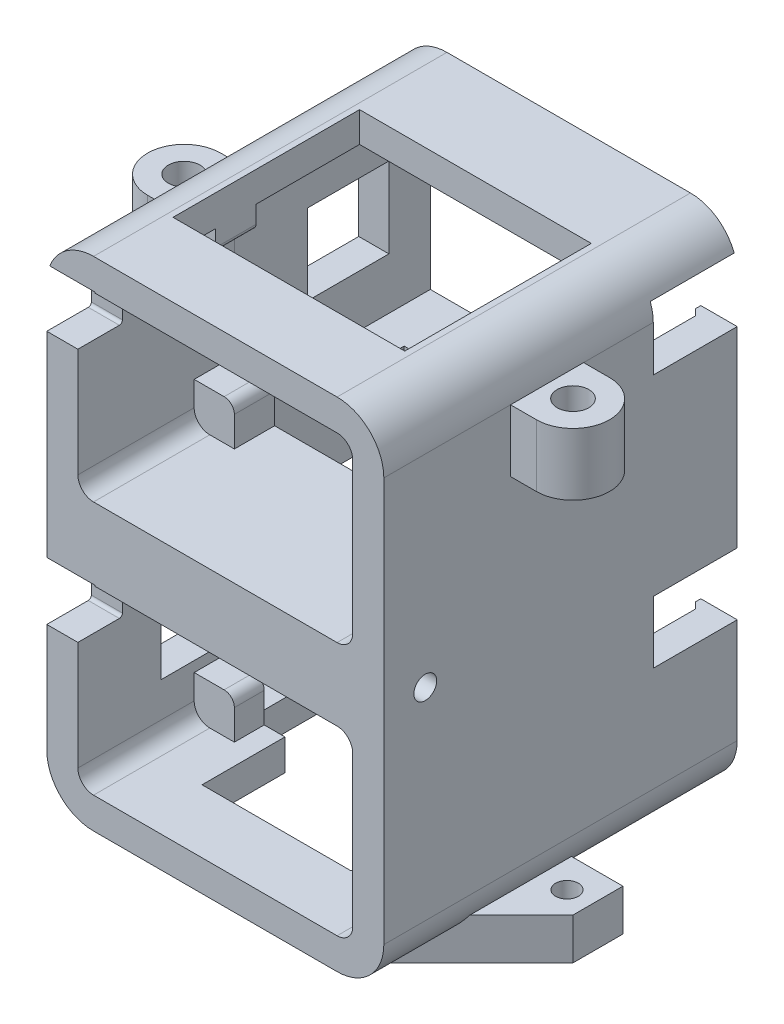
SolidWorks part; units mm, degrees
ref_plane "前视基准面" through (0, 0, 0) normal (0, 0, 1) x (1, 0, 0)
ref_plane "上视基准面" through (0, 0, 0) normal (0, 1, 0) x (1, 0, 0)
ref_plane "右视基准面" through (0, 0, 0) normal (1, 0, 0) x (0, 0, -1)
other "Configuration Table"
sketch "草图2" plane through (0, 0, 0) normal (0, 0, 1) x (1, 0, 0)
  line L20 (13.26, -7.25) -> (13.26, 7.25)
  line L21 (11.75, 8.76) -> (-16.76, 8.76)
  line L22 (-16.76, 8.76) -> (-16.76, 3.34)
  line L23 (-16.76, 3.34) -> (-13.26, 3.34)
  line L24 (-13.26, 3.34) -> (-13.26, -7.25)
  line L25 (-11.75, -8.76) -> (-3.99, -8.76)
  line L26 (-3.99, -8.76) -> (-3.99, -7.76)
  line L27 (-3.99, -7.76) -> (3.99, -7.76)
  line L28 (3.99, -7.76) -> (3.99, -8.76)
  line L29 (3.99, -8.76) -> (11.75, -8.76)
  line L40 (13.26, -7.25) -> (13.26, 7.25)
  line L41 (11.75, 8.76) -> (-16.76, 8.76)
  line L42 (-16.76, 8.76) -> (-16.76, 3.34)
  line L43 (-16.76, 3.34) -> (-13.26, 3.34)
  line L44 (-13.26, 3.34) -> (-13.26, -7.25)
  line L45 (-11.75, -8.76) -> (-3.99, -8.76)
  line L49 (3.99, -8.76) -> (11.75, -8.76)
  line L50 (-3.99, 15.74) -> (3.99, 15.74)
  line L51 (-3.99, -8.76) -> (3.99, -8.76)
  line L52 (-3.99, 12.74) -> (3.99, 12.74)
  line L53 (3.99, 12.74) -> (11.75, 12.74)
  line L54 (16.26, 17.25) -> (16.26, 31.75)
  line L55 (11.75, 36.26) -> (-19.76, 36.26)
  line L56 (-19.76, 36.26) -> (-19.76, 24.84)
  line L57 (-19.76, 24.84) -> (-16.26, 24.84)
  line L58 (-16.26, 24.84) -> (-16.26, 17.25)
  line L59 (-11.75, 12.74) -> (-3.99, 12.74)
  line L70 (13.26, 17.25) -> (13.26, 31.75)
  line L71 (11.75, 33.26) -> (-16.76, 33.26)
  line L72 (-16.76, 33.26) -> (-16.76, 27.84)
  line L73 (-16.76, 27.84) -> (-13.26, 27.84)
  line L74 (-13.26, 27.84) -> (-13.26, 17.25)
  line L75 (-11.75, 15.74) -> (-3.99, 15.74)
  line L76 (-3.99, 15.74) -> (-3.99, 16.74)
  line L77 (-3.99, 16.74) -> (3.99, 16.74)
  line L78 (3.99, 16.74) -> (3.99, 15.74)
  line L79 (3.99, 15.74) -> (11.75, 15.74)
  line L80 (13.26, 17.25) -> (13.26, 31.75)
  line L81 (11.75, 33.26) -> (-16.76, 33.26)
  line L82 (-16.76, 33.26) -> (-16.76, 27.84)
  line L83 (-16.76, 27.84) -> (-13.26, 27.84)
  line L84 (-13.26, 27.84) -> (-13.26, 17.25)
  line L85 (-11.75, 15.74) -> (-3.99, 15.74)
  line L89 (3.99, 15.74) -> (11.75, 15.74)
  line L90 (16.26, -7.25) -> (16.26, 7.25)
  line L91 (11.75, 11.76) -> (-19.76, 11.76)
  line L92 (-19.76, 11.76) -> (-19.76, 0.34)
  line L93 (-19.76, 0.34) -> (-16.26, 0.34)
  line L94 (-16.26, 0.34) -> (-16.26, -7.25)
  line L95 (-11.75, -11.76) -> (-3.99, -11.76)
  line L96 (-3.99, -11.76) -> (3.99, -11.76)
  line L97 (3.99, -11.76) -> (11.75, -11.76)
  line L98 (-16.26, 0.34) -> (-16.26, 3.34)
  line L99 (-16.26, 17.25) -> (-16.26, 11.76)
  line L100 (16.26, 17.25) -> (16.26, 7.25)
  line L101 (-16.76, 33.26) -> (-19.76, 33.26)
  line L102 (-16.76, 27.84) -> (-19.76, 27.84)
  line L103 (-16.76, 8.76) -> (-19.76, 8.76)
  line L104 (-16.26, 24.84) -> (-16.26, 27.84)
  line L105 (-16.26, 36.26) -> (-16.26, 33.26)
  line L106 (-16.26, 11.76) -> (-16.26, 8.76)
  line L107 (-16.26, 33.26) -> (-16.26, 27.84)
  line L108 (-16.26, 8.76) -> (-16.26, 3.34)
  line L109 (-13.26, 27.84) -> (-13.26, 33.26)
  line L110 (-13.26, 3.34) -> (-13.26, 8.76)
  arc A1 (-11.75, 11.76) -> (-16.26, 7.25) centre (-11.75, 7.25) ccw
  arc A2 (-11.75, 8.76) -> (-13.26, 7.25) centre (-11.75, 7.25) ccw
  arc A3 (-11.75, 8.76) -> (-13.26, 7.25) centre (-11.75, 7.25) ccw
  arc A6 (13.26, 7.25) -> (11.75, 8.76) centre (11.75, 7.25) ccw
  arc A7 (-13.26, -7.25) -> (-11.75, -8.76) centre (-11.75, -7.25) ccw
  arc A8 (11.75, -8.76) -> (13.26, -7.25) centre (11.75, -7.25) ccw
  arc A12 (13.26, 7.25) -> (11.75, 8.76) centre (11.75, 7.25) ccw
  arc A13 (-13.26, -7.25) -> (-11.75, -8.76) centre (-11.75, -7.25) ccw
  arc A14 (11.75, -8.76) -> (13.26, -7.25) centre (11.75, -7.25) ccw
  arc A15 (11.75, 12.74) -> (16.26, 17.25) centre (11.75, 17.25) ccw
  arc A16 (16.26, 31.75) -> (11.75, 36.26) centre (11.75, 31.75) ccw
  arc A17 (-16.26, 17.25) -> (-11.75, 12.74) centre (-11.75, 17.25) ccw
  arc A21 (13.26, 31.75) -> (11.75, 33.26) centre (11.75, 31.75) ccw
  arc A22 (-13.26, 17.25) -> (-11.75, 15.74) centre (-11.75, 17.25) ccw
  arc A23 (11.75, 15.74) -> (13.26, 17.25) centre (11.75, 17.25) ccw
  arc A24 (13.26, 31.75) -> (11.75, 33.26) centre (11.75, 31.75) ccw
  arc A25 (-13.26, 17.25) -> (-11.75, 15.74) centre (-11.75, 17.25) ccw
  arc A26 (11.75, 15.74) -> (13.26, 17.25) centre (11.75, 17.25) ccw
  arc A27 (16.26, 7.25) -> (11.75, 11.76) centre (11.75, 7.25) ccw
  arc A28 (-16.26, -7.25) -> (-11.75, -11.76) centre (-11.75, -7.25) ccw
  arc A29 (11.75, -11.76) -> (16.26, -7.25) centre (11.75, -7.25) ccw
  arc A31 (-11.75, 36.26) -> (-16.26, 31.75) centre (-11.75, 31.75) ccw
  arc A32 (-11.75, 33.26) -> (-13.26, 31.75) centre (-11.75, 31.75) ccw
  arc A33 (-11.75, 33.26) -> (-13.26, 31.75) centre (-11.75, 31.75) ccw
  dimension "D3" = 3
  dimension "D4" = 3
  dimension "D5" = 0.01
  dimension "D6" = 3
  dimension "D7" = 0.01
  dimension "D8" = 3
extrude "凸台-拉伸2" add sketch "草图2" against normal up to surface (11.22 mm away)
sketch "草图3" plane through (0, 0, -11.22) normal (0, 0, -1) x (-1, 0, 0)
  line L0 (11.75, -8.76) -> (-11.75, -8.76) construction
  line L2 (-11.75, 8.76) -> (11.75, 8.76) construction
  line L3 (11.75, -8.76) -> (-11.75, -8.76)
  line L4 (16.26, -7.25) -> (16.26, 31.75)
  line L5 (11.75, 36.26) -> (-11.75, 36.26)
  line L6 (-16.26, 31.75) -> (-16.26, -7.25)
  line L7 (-11.75, -11.76) -> (11.75, -11.76)
  line L12 (16.26, -7.25) -> (16.26, 31.75)
  line L13 (11.75, 36.26) -> (-11.75, 36.26)
  line L14 (-16.26, 31.75) -> (-16.26, -7.25)
  line L16 (-11.75, -11.76) -> (11.75, -11.76)
  line L20 (-13.26, -7.25) -> (-13.26, 7.25)
  line L21 (-11.75, 33.26) -> (11.75, 33.26) construction
  line L22 (-13.26, 17.25) -> (-13.26, 31.75) construction
  line L23 (-9.38, -8.74) -> (-9.38, -5.87)
  line L24 (-10.37, -4.88) -> (-13.24, -4.88)
  line L25 (-13.24, -4.88) -> (-13.24, -7.25)
  line L26 (-11.75, -8.74) -> (-9.38, -8.74)
  line L27 (-9.38, -8.74) -> (-9.38, -5.87)
  line L28 (-10.37, -4.88) -> (-13.24, -4.88)
  line L32 (11.75, 15.74) -> (-11.75, 15.74) construction
  line L33 (-11.75, 33.26) -> (11.75, 33.26)
  line L34 (-13.26, 17.25) -> (-13.26, 31.75)
  line L36 (11.75, 15.74) -> (-11.75, 15.74)
  line L38 (13.26, 7.25) -> (13.26, -7.25) construction
  line L39 (13.24, -4.88) -> (10.37, -4.88)
  line L40 (9.38, -5.87) -> (9.38, -8.74)
  line L41 (9.38, -8.74) -> (11.75, -8.74)
  line L42 (13.24, -7.25) -> (13.24, -4.88)
  line L43 (13.24, -4.88) -> (10.37, -4.88)
  line L44 (9.38, -5.87) -> (9.38, -8.74)
  line L47 (13.26, 7.25) -> (13.26, -7.25)
  line L48 (-11.75, 8.76) -> (11.75, 8.76) construction
  line L49 (-9.38, 15.75) -> (-9.38, 18.63)
  line L50 (-10.37, 19.62) -> (-13.25, 19.62)
  line L51 (-13.24, 6.68) -> (-11.67, 6.68)
  line L52 (-11.18, 7.17) -> (-11.18, 8.74)
  line L53 (-11.18, 8.74) -> (-11.75, 8.74)
  line L54 (-13.24, 7.25) -> (-13.24, 6.68)
  line L55 (-13.24, 6.68) -> (-11.67, 6.68)
  line L56 (-11.18, 7.17) -> (-11.18, 8.74)
  line L59 (-13.24, 6.68) -> (-13.26, 6.68)
  line L60 (-13.26, -7.25) -> (-13.26, 7.25) construction
  line L61 (-9.38, 15.74) -> (-9.38, 18.63)
  line L62 (-10.37, 19.62) -> (-13.26, 19.62)
  line L63 (11.18, 8.74) -> (11.18, 7.17)
  line L64 (11.67, 6.68) -> (13.24, 6.68)
  line L65 (13.24, 6.68) -> (13.24, 7.25)
  line L66 (11.75, 8.74) -> (11.18, 8.74)
  line L67 (11.18, 8.76) -> (11.18, 7.17)
  line L68 (11.67, 6.68) -> (13.26, 6.68)
  line L71 (-11.75, 8.76) -> (11.75, 8.76)
  line L73 (-13.25, 31.18) -> (-11.67, 31.18)
  line L74 (-11.18, 31.67) -> (-11.18, 33.25)
  line L75 (-13.25, 31.18) -> (-11.67, 31.18)
  line L76 (-11.18, 31.67) -> (-11.18, 33.25)
  line L79 (11.67, 31.18) -> (13.25, 31.18)
  line L80 (11.18, 33.25) -> (11.18, 31.67)
  line L81 (11.67, 31.18) -> (13.26, 31.18)
  line L82 (11.18, 33.25) -> (11.18, 31.67)
  line L83 (-13.25, 31.18) -> (-13.26, 31.18)
  line L84 (-11.18, 33.25) -> (-11.18, 33.26)
  line L85 (9.38, 18.63) -> (9.38, 15.75)
  line L86 (13.25, 19.62) -> (10.37, 19.62)
  line L87 (9.38, 18.63) -> (9.38, 15.74)
  line L88 (13.26, 19.62) -> (10.37, 19.62)
  line L89 (11.18, 33.25) -> (11.18, 33.26)
  line L90 (-11.18, 8.74) -> (-11.18, 8.76)
  line L91 (13.26, 31.75) -> (13.26, 17.25) construction
  line L92 (13.26, 31.75) -> (13.26, 17.25)
  line L93 (-13.24, -4.88) -> (-13.26, -4.88)
  line L94 (-9.38, -8.74) -> (-9.38, -8.76)
  line L95 (9.38, -8.74) -> (9.38, -8.76)
  line L96 (13.24, -4.88) -> (13.26, -4.88)
  arc A0 (-13.26, -7.25) -> (-11.75, -8.76) centre (-11.75, -7.25) ccw construction
  arc A1 (11.75, -8.76) -> (13.26, -7.25) centre (11.75, -7.25) ccw construction
  arc A2 (-11.75, 8.76) -> (-13.26, 7.25) centre (-11.75, 7.25) ccw construction
  arc A3 (11.75, -11.76) -> (16.26, -7.25) centre (11.75, -7.25) ccw
  arc A4 (-11.75, 36.26) -> (-16.26, 31.75) centre (-11.75, 31.75) ccw
  arc A5 (-16.26, -7.25) -> (-11.75, -11.76) centre (-11.75, -7.25) ccw
  arc A6 (11.75, -11.76) -> (16.26, -7.25) centre (11.75, -7.25) ccw
  arc A9 (-11.75, 36.26) -> (-16.26, 31.75) centre (-11.75, 31.75) ccw
  arc A10 (-9.38, -5.87) -> (-10.37, -4.88) centre (-10.37, -5.87) ccw
  arc A11 (-13.24, -7.25) -> (-11.75, -8.74) centre (-11.75, -7.25) ccw
  arc A12 (-9.38, -5.87) -> (-10.37, -4.88) centre (-10.37, -5.87) ccw
  arc A14 (-16.26, -7.25) -> (-11.75, -11.76) centre (-11.75, -7.25) ccw
  arc A15 (-13.26, -7.25) -> (-11.75, -8.76) centre (-11.75, -7.25) ccw
  arc A16 (11.75, -8.76) -> (13.26, -7.25) centre (11.75, -7.25) ccw
  arc A17 (-11.75, 8.76) -> (-13.26, 7.25) centre (-11.75, 7.25) ccw
  arc A18 (10.37, -4.88) -> (9.38, -5.87) centre (10.37, -5.87) ccw
  arc A19 (11.75, -8.74) -> (13.24, -7.25) centre (11.75, -7.25) ccw
  arc A20 (10.37, -4.88) -> (9.38, -5.87) centre (10.37, -5.87) ccw
  arc A22 (-11.75, 33.26) -> (-13.26, 31.75) centre (-11.75, 31.75) ccw construction
  arc A23 (11.75, 15.74) -> (13.26, 17.25) centre (11.75, 17.25) ccw construction
  arc A24 (-11.67, 6.68) -> (-11.18, 7.17) centre (-11.67, 7.17) ccw
  arc A25 (-11.75, 8.74) -> (-13.24, 7.25) centre (-11.75, 7.25) ccw
  arc A26 (-11.67, 6.68) -> (-11.18, 7.17) centre (-11.67, 7.17) ccw
  arc A28 (-13.26, 17.25) -> (-11.75, 15.74) centre (-11.75, 17.25) ccw construction
  arc A29 (-11.75, 33.26) -> (-13.26, 31.75) centre (-11.75, 31.75) ccw
  arc A30 (11.18, 7.17) -> (11.67, 6.68) centre (11.67, 7.17) ccw
  arc A31 (13.24, 7.25) -> (11.75, 8.74) centre (11.75, 7.25) ccw
  arc A32 (11.18, 7.17) -> (11.67, 6.68) centre (11.67, 7.17) ccw
  arc A34 (11.75, 15.74) -> (13.26, 17.25) centre (11.75, 17.25) ccw
  arc A35 (-13.26, 17.25) -> (-11.75, 15.74) centre (-11.75, 17.25) ccw
  arc A36 (13.26, 7.25) -> (11.75, 8.76) centre (11.75, 7.25) ccw construction
  arc A37 (13.26, 7.25) -> (11.75, 8.76) centre (11.75, 7.25) ccw
  arc A38 (-9.38, 18.63) -> (-10.37, 19.62) centre (-10.37, 18.63) ccw
  arc A39 (-9.38, 18.63) -> (-10.37, 19.62) centre (-10.37, 18.63) ccw
  arc A41 (-11.67, 31.18) -> (-11.18, 31.67) centre (-11.67, 31.67) ccw
  arc A42 (-11.67, 31.18) -> (-11.18, 31.67) centre (-11.67, 31.67) ccw
  arc A44 (11.18, 31.67) -> (11.67, 31.18) centre (11.67, 31.67) ccw
  arc A45 (11.18, 31.67) -> (11.67, 31.18) centre (11.67, 31.67) ccw
  arc A46 (13.26, 31.75) -> (11.75, 33.26) centre (11.75, 31.75) ccw construction
  arc A47 (10.37, 19.62) -> (9.38, 18.63) centre (10.37, 18.63) ccw
  arc A48 (10.37, 19.62) -> (9.38, 18.63) centre (10.37, 18.63) ccw
  arc A49 (13.26, 31.75) -> (11.75, 33.26) centre (11.75, 31.75) ccw
  arc A52 (16.26, 31.75) -> (11.75, 36.26) centre (11.75, 31.75) ccw
  arc A53 (16.26, 31.75) -> (11.75, 36.26) centre (11.75, 31.75) ccw
  dimension "D7" = 0.01
  dimension "D9" = 0.01
extrude "凸台-拉伸3" add sketch "草图3" along normal up to surface (3.88 mm away)
sketch "草图4" plane through (-16.26, 0, 0) normal (-1, 0, 0) x (0, 0, 1)
  line L8 (0.1, 8.85) -> (-4, 8.85)
  line L9 (-4.3, 8.55) -> (-4.3, 3.55)
  line L10 (-4, 3.25) -> (0.1, 3.25)
  line L11 (0.1, 3.25) -> (0.1, 8.85)
  line L12 (0.1, 8.85) -> (-4, 8.85)
  line L13 (-4.3, 8.55) -> (-4.3, 3.55)
  line L14 (-4, 3.25) -> (0.1, 3.25)
  line L15 (0.1, 3.25) -> (0.1, 8.85)
  line L20 (0.1, 33.35) -> (-4, 33.35)
  line L21 (-4.3, 33.05) -> (-4.3, 28.05)
  line L22 (-4, 27.75) -> (0.1, 27.75)
  line L23 (0.1, 27.75) -> (0.1, 33.35)
  line L24 (0.1, 33.35) -> (-4, 33.35)
  line L25 (-4.3, 33.05) -> (-4.3, 28.05)
  line L26 (-4, 27.75) -> (0.1, 27.75)
  line L27 (0.1, 27.75) -> (0.1, 33.35)
  arc A4 (-4, 8.85) -> (-4.3, 8.55) centre (-4, 8.55) ccw
  arc A5 (-4.3, 3.55) -> (-4, 3.25) centre (-4, 3.55) ccw
  arc A6 (-4, 8.85) -> (-4.3, 8.55) centre (-4, 8.55) ccw
  arc A7 (-4.3, 3.55) -> (-4, 3.25) centre (-4, 3.55) ccw
  arc A10 (-4, 33.35) -> (-4.3, 33.05) centre (-4, 33.05) ccw
  arc A11 (-4.3, 28.05) -> (-4, 27.75) centre (-4, 28.05) ccw
  arc A12 (-4, 33.35) -> (-4.3, 33.05) centre (-4, 33.05) ccw
  arc A13 (-4.3, 28.05) -> (-4, 27.75) centre (-4, 28.05) ccw
  dimension "D1" = 0.1
extrude "切除-拉伸1" cut sketch "草图4" against normal blind 4.65
ref_plane "基准面1" through (0, 31.75, 0) normal (0, 1, 0) x (1, 0, 0)
sketch "草图8" plane through (0, 31.75, 0) normal (0, 1, 0) x (1, 0, 0)
  line L0 (18.76, 12.23) -> (15.235, 12.23)
  line L1 (15.235, 12.23) -> (15.235, 15.755)
  line L2 (16.26, 15.1) -> (16.26, 0) construction
  line L3 (-12.113, 15.755) -> (15.235, 15.755) construction
  line L4 (9.73, 15.91) -> (-9.73, 15.91) construction
  line L5 (-9.73, 15.6) -> (9.73, 15.6) construction
  line L9 (18.76, 19.28) -> (15.235, 19.28)
  line L10 (15.235, 15.755) -> (15.235, 19.28)
  circle A2 centre (18.76, 15.755) radius 1.525
  circle A3 centre (18.76, 15.755) radius 3.525
  dimension "D1" = 3.05
  dimension "D3" = 2.5
  dimension "D2" = 2
extrude "凸台-拉伸5" add sketch "草图8" against normal blind 6 contours A3 A2 | A3 L9 L10 | A3 L1 L0
mirror "镜向1" about plane through (0, 0, 0) normal (1, 0, 0) of "凸台-拉伸5"
sketch "草图9" plane through (0, 0, -15.1) normal (0, 0, -1) x (-1, 0, 0)
  line L0 (-11.18, 33.26) -> (11.18, 33.26) construction
  line L1 (-11.18, 33.26) -> (11.18, 33.26)
  line L2 (-11.18, 33.26) -> (-11.18, 36.26)
  line L3 (-11.18, 36.26) -> (11.18, 36.26)
  line L4 (11.18, 33.26) -> (11.18, 36.26)
  line L5 (11.75, 36.26) -> (-11.75, 36.26) construction
  line L6 (-11.18, 31.67) -> (-11.18, 33.26) construction
  line L7 (11.18, 33.26) -> (11.18, 31.67) construction
extrude "切除-拉伸3" cut sketch "草图9" against normal blind 8
sketch "草图10" plane through (0, 0, -15.1) normal (0, 0, -1) x (-1, 0, 0)
  line L0 (-11.75, -11.76) -> (11.75, -11.76) construction
  line L1 (-10.73, -11.76) -> (10.73, -11.76)
  line L2 (-10.73, -11.76) -> (-10.73, -4.88)
  line L3 (-10.73, -4.88) -> (10.73, -4.88)
  line L4 (10.73, -11.76) -> (10.73, -4.88)
  line L5 (13.26, -4.88) -> (10.37, -4.88) construction
  line L6 (-9.73, 21.7989) -> (-9.73, 20.8989) construction
  line L7 (9.73, 69.5489) -> (9.73, -48.1511) construction
  dimension "D1" = 1
  dimension "D2" = 1
extrude "切除-拉伸4" cut sketch "草图10" against normal blind 1
sketch "草图12" plane through (-16.26, 0, 0) normal (-1, 0, 0) x (0, 0, 1)
  line L0 (0, 8.85) -> (0, 27.75) construction
  line L1 (-11.22, 8.76) -> (-4.2142, 8.76) construction
  line L2 (-11.22, 15.74) -> (0, 15.74) construction
  line L3 (-11.22, 8.76) -> (-4.2142, 8.76)
  line L4 (-11.22, 15.74) -> (0, 15.74)
  line L5 (-8.8508, 12.25) -> (0.722, 12.25) construction
  circle A0 centre (-4, 12.25) radius 1.1
  dimension "D1" = 2.2
  dimension "D2" = 4
extrude "切除-拉伸5" cut sketch "草图12" against normal blind 8 contours A0 L5 | L5 A0
mirror "镜向2" about plane through (0, 0, 0) normal (1, 0, 0) of "切除-拉伸5"
sketch "草图14" plane through (0, 0, -15.1) normal (0, 0, -1) x (-1, 0, 0)
  line L0 (-16.26, 19.53) -> (16.26, 19.53)
  line L2 (-16.26, 8.85) -> (16.26, 8.85)
  line L3 (-10.37, 19.63) -> (-13.25, 19.63) construction
  line L6 (9.88, -48.3011) -> (9.88, 69.6193)
  line L7 (-9.88, -48.3011) -> (9.88, -48.3011)
  line L8 (-9.88, 69.6193) -> (-9.88, -48.3011)
  line L9 (9.88, -48.3011) -> (9.88, 69.6193)
  line L10 (-9.88, -48.3011) -> (9.88, -48.3011)
  line L11 (-9.88, 69.6193) -> (-9.88, -48.3011)
  line L13 (-11.17, 8.75) -> (11.17, 8.75) construction
  line L19 (16.26, 3.25) -> (13.26, 3.25)
  line L20 (16.26, -7.25) -> (16.26, 3.25)
  line L21 (-11.75, -11.76) -> (11.75, -11.76)
  line L22 (-16.26, 31.75) -> (-16.26, -7.25)
  line L23 (11.75, 36.26) -> (-11.75, 36.26)
  line L24 (11.61, 33.35) -> (15.9666, 33.35)
  line L26 (-11.75, 33.26) -> (11.61, 33.26)
  line L27 (-13.26, 17.25) -> (-13.26, 31.75)
  line L28 (11.75, 15.74) -> (-11.75, 15.74)
  line L29 (13.26, 27.75) -> (13.26, 17.25)
  line L30 (16.26, 27.75) -> (13.26, 27.75)
  line L31 (16.26, 8.85) -> (16.26, 27.75)
  line L32 (11.61, 8.85) -> (16.26, 8.85)
  line L34 (-11.75, 8.76) -> (11.61, 8.76)
  line L35 (-13.26, -7.25) -> (-13.26, 7.25)
  line L36 (11.75, -8.76) -> (-11.75, -8.76)
  line L37 (13.26, 3.25) -> (13.26, -7.25)
  line L39 (16.26, -7.25) -> (16.26, 8.85)
  line L40 (-11.75, -11.76) -> (11.75, -11.76)
  line L41 (-16.26, 31.75) -> (-16.26, -7.25)
  line L42 (11.75, 36.26) -> (-11.75, 36.26)
  line L50 (16.26, 8.85) -> (16.26, 31.75)
  line L66 (11.61, 33.26) -> (11.61, 33.35)
  line L67 (11.61, 8.76) -> (11.61, 8.85)
  arc A2 (9.88, 69.6193) -> (-9.88, 69.6193) centre (0, 57.7742) ccw
  arc A3 (9.88, 69.6193) -> (-9.88, 69.6193) centre (0, 57.7742) ccw
  arc A10 (11.75, -11.76) -> (16.26, -7.25) centre (11.75, -7.25) ccw
  arc A11 (-16.26, -7.25) -> (-11.75, -11.76) centre (-11.75, -7.25) ccw
  arc A12 (-11.75, 36.26) -> (-16.26, 31.75) centre (-11.75, 31.75) ccw
  arc A13 (15.9666, 33.35) -> (11.75, 36.26) centre (11.75, 31.75) ccw
  arc A14 (-11.75, 33.26) -> (-13.26, 31.75) centre (-11.75, 31.75) ccw
  arc A15 (-13.26, 17.25) -> (-11.75, 15.74) centre (-11.75, 17.25) ccw
  arc A16 (11.75, 15.74) -> (13.26, 17.25) centre (11.75, 17.25) ccw
  arc A17 (-11.75, 8.76) -> (-13.26, 7.25) centre (-11.75, 7.25) ccw
  arc A18 (-13.26, -7.25) -> (-11.75, -8.76) centre (-11.75, -7.25) ccw
  arc A19 (11.75, -8.76) -> (13.26, -7.25) centre (11.75, -7.25) ccw
  arc A20 (11.75, -11.76) -> (16.26, -7.25) centre (11.75, -7.25) ccw
  arc A21 (-16.26, -7.25) -> (-11.75, -11.76) centre (-11.75, -7.25) ccw
  arc A22 (-11.75, 36.26) -> (-16.26, 31.75) centre (-11.75, 31.75) ccw
  arc A23 (16.26, 31.75) -> (11.75, 36.26) centre (11.75, 31.75) ccw
  dimension "D3" = 0.1
  dimension "D4" = 0.1
  dimension "D2" = 0.15
extrude "凸台-拉伸7" add sketch "草图14" along normal blind 3
sketch "草图15" plane through (0, 0, -15.1) normal (0, 0, -1) x (-1, 0, 0)
  line L0 (-16.26, 25.75) -> (-16.26, 19.53) construction
  line L7 (-16.26, 19.53) -> (-16.26, 8.85) construction
  line L8 (-16.26, 8.85) -> (-16.26, -7.25) construction
  line L10 (-10.73, -11.76) -> (10.73, -11.76) construction
  line L22 (16.26, -7.25) -> (16.26, 8.85) construction
  line L23 (16.26, 8.85) -> (16.26, 19.53) construction
  line L32 (16.26, 19.53) -> (16.26, 25.75) construction
  line L37 (11.18, 36.26) -> (-11.18, 36.26) construction
  line L38 (-16.26, 31.75) -> (-16.26, 19.53)
  line L39 (-16.26, 19.53) -> (-16.26, 8.85)
  line L42 (-16.26, 8.85) -> (-16.26, -7.25)
  line L43 (-11.75, -11.76) -> (11.75, -11.76)
  line L44 (16.26, -7.25) -> (16.26, 8.85)
  line L45 (16.26, 8.85) -> (16.26, 19.53)
  line L46 (16.26, 19.53) -> (16.26, 31.75)
  line L47 (11.75, 36.26) -> (-11.75, 36.26)
  line L48 (-11.17, 33.25) -> (11.17, 33.25) construction
  line L49 (-13.35, 33.35) -> (13.35, 33.35)
  line L54 (-13.35, 33.35) -> (-13.35, -8.85)
  line L55 (-13.35, -8.85) -> (13.35, -8.85)
  line L56 (13.35, 33.35) -> (13.35, -8.85)
  line L58 (13.25, 6.67) -> (13.25, -4.87) construction
  line L59 (9.37, -8.75) -> (-9.37, -8.75) construction
  line L60 (-13.25, -4.87) -> (-13.25, 6.67) construction
  arc A8 (-16.26, -7.25) -> (-11.75, -11.76) centre (-11.75, -7.25) ccw construction
  arc A9 (11.75, -11.76) -> (16.26, -7.25) centre (11.75, -7.25) ccw construction
  arc A10 (16.26, 31.75) -> (11.75, 36.26) centre (11.75, 31.75) ccw construction
  arc A11 (-11.75, 36.26) -> (-16.26, 31.75) centre (-11.75, 31.75) ccw construction
  arc A12 (-16.26, -7.25) -> (-11.75, -11.76) centre (-11.75, -7.25) ccw
  arc A13 (11.75, -11.76) -> (16.26, -7.25) centre (11.75, -7.25) ccw
  arc A14 (16.26, 31.75) -> (11.75, 36.26) centre (11.75, 31.75) ccw
  arc A15 (-11.75, 36.26) -> (-16.26, 31.75) centre (-11.75, 31.75) ccw
  point P2 (13.45, 33.102)
  point P29 (-13.45, 33.1809)
  point P38 (-13.45, 15.55)
  dimension "D2" = 0.1
  dimension "D1" = 0.1
  dimension "D3" = 0.1
  dimension "D4" = 0.1
extrude "凸台-上半部分" add sketch "草图15" along normal blind 19
sketch "草图16" plane through (0, 0, -18.1) normal (0, 0, -1) x (-1, 0, 0)
  line L1 (-13.35, 8.85) -> (13.35, 8.85)
  line L2 (-13.35, 8.85) -> (-13.35, 15.65)
  line L3 (-13.35, 15.65) -> (13.35, 15.65)
  line L4 (13.35, 8.85) -> (13.35, 15.65)
  line L12 (-13.35, 33.35) -> (-13.35, -8.85) construction
  line L13 (13.35, 33.35) -> (13.35, -8.85) construction
  line L15 (-4, 15.75) -> (-11.75, 15.75) construction
  line L16 (-11.17, 8.75) -> (11.17, 8.75) construction
  point P4 (0, 0)
  point P5 (-13.45, 15.74)
  point P7 (13.45, 8.76)
  point P12 (0, 0)
  dimension "D2" = 0.1
  dimension "D1" = 0.1
extrude "凸台-拉伸9" add sketch "草图16" along normal up to surface (16 mm away) up to face at (0, 12.25, -34.1)
sketch "草图11" plane through (0, -13.58, 0) normal (0, 1, 0) x (1, 0, 0)
  line L2 (11.75, 34.1) -> (11.75, 0)
  line L3 (11.75, 34.1) -> (11.75, 0) construction
  line L7 (15.88, 21.655) -> (15.88, 16.405)
  line L8 (15.88, 16.405) -> (17.4201, 16.405)
  line L9 (17.4201, 15.105) -> (15.88, 15.105)
  line L10 (15.88, 15.105) -> (15.88, 9.855)
  line L11 (15.88, 9.855) -> (20.58, 9.855)
  line L12 (20.58, 9.855) -> (20.58, 21.655)
  line L13 (20.58, 21.655) -> (15.88, 21.655)
  line L19 (20.58, 13.9124) -> (20.58, 18.755)
  line L21 (11.75, 18.755) -> (20.58, 18.755)
  line L22 (20.58, 13.9124) -> (11.75, 5.0824)
  circle A0 centre (18.18, 15.755) radius 1.1
  arc A1 (17.4201, 15.105) -> (17.4201, 16.405) centre (18.18, 15.755) ccw
  line M15 (15.88, 21.655) -> (15.88, 16.405)
  line M16 (15.88, 16.405) -> (17.4201, 16.405)
  line M18 (17.4201, 15.105) -> (15.88, 15.105)
  line M19 (15.88, 15.105) -> (15.88, 9.855)
  line M20 (15.88, 9.855) -> (20.58, 9.855)
  line M21 (20.58, 9.855) -> (20.58, 21.655)
  dimension "D6" = 2.2
  dimension "D2" = 3
  dimension "D5" = 45
  dimension "D7" = 3
  dimension "D1" = 0
extrude "凸台-舵机固定孔位" add sketch "草图11" along normal blind 4 contours A0 L21 L2 L22 M16 M15 M20 M19 M18 | A0 L22 L21 M18 M19 M20 M21 M15 M16
sketch "草图17" plane through (0, 8.85, 0) normal (0, -1, 0) x (1, 0, 0)
  line L2 (11.75, -34.1) -> (-11.75, -34.1) construction
  line L3 (-9.88, -18.1) -> (9.88, -18.1)
  line L5 (-9.88, -18.1) -> (9.88, -18.1)
  line L6 (-9.88, -18.1) -> (-9.88, -28.1)
  line L7 (-9.88, -28.1) -> (9.88, -28.1)
  line L8 (9.88, -18.1) -> (9.88, -28.1)
  line L9 (9.88, -18.1) -> (9.88, -15.1) construction
  line L10 (9.88, -18.1) -> (-9.88, -18.1) construction
  line L12 (-9.88, -18.1) -> (-9.88, -15.1) construction
  point P1 (9.88, -18.1)
  point P2 (9.88, -18.1)
  point P4 (0, 0)
  point P12 (-10.2095, -18.1)
  point P13 (-9.88, -18.1)
  point P15 (0, 0)
  point P16 (0, 0)
  point P17 (9.88, -17.8358)
  point P20 (9.88, -18.1489)
  point P21 (9.88, -18.1)
  point P26 (-9.88, -18.1)
  dimension "D1" = 6
extrude "切除-拉伸8" cut sketch "草图17" against normal up to next contours L8 L3 L6 L7
sketch "草图18" plane through (13.35, 0, 0) normal (-1, 0, 0) x (0, 0, 1)
  line L0 (0, -7.25) -> (0, 31.75) construction
  line L1 (-34.1, 2.85) -> (-26, 2.85)
  line L2 (-34.1, 2.85) -> (-34.1, 8.85)
  line L3 (-34.1, 8.85) -> (-26, 8.85)
  line L4 (-26, 2.85) -> (-26, 8.85)
  line L5 (-34.1, 27.35) -> (-26, 27.35)
  line L6 (-34.1, 27.35) -> (-34.1, 33.35)
  line L7 (-34.1, 33.35) -> (-26, 33.35)
  line L8 (-26, 27.35) -> (-26, 33.35)
  line L9 (-34.1, -7.25) -> (-34.1, 31.75) construction
  line L10 (-34.1, 8.85) -> (-34.1, -8.85) construction
  line L11 (-34.1, 8.85) -> (-15.1, 8.85) construction
  point P4 (-34.1, 8.95)
  point P9 (-34.1, 8.95)
  point P10 (0, 0)
  point P16 (-34.1, 8.7623)
  point P19 (-34.1, 8.2941)
  point P20 (-34.1, 8.0806)
  point P21 (-34.1, 8.76)
  point P23 (0, 0)
  point P24 (-34.1, 33.45)
  point P26 (0, 0)
  point P27 (-34.1, 9.75)
  point P30 (-34.1, 8.8694)
  point P31 (-34.1, 9.75)
  dimension "D2" = 6
  dimension "D3" = 6
  dimension "D5" = 26
extrude "切除-拉伸9" cut sketch "草图18" against normal up to next
sketch "草图19" plane through (0, -11.76, 0) normal (0, -1, 0) x (1, 0, 0)
  line L1 (-10.73, -14.1) -> (10.73, -14.1)
  line L2 (-10.73, -14.1) -> (-10.73, -15.1)
  line L3 (-10.73, -15.1) -> (10.73, -15.1)
  line L4 (10.73, -14.1) -> (10.73, -15.1)
  line L5 (-10.73, -15.1) -> (10.73, -15.1)
  line L6 (-10.73, -15.1) -> (-10.73, -25.1)
  line L7 (-10.73, -25.1) -> (10.73, -25.1)
  line L8 (10.73, -15.1) -> (10.73, -25.1)
  point P8 (0, 0)
  point P9 (10.73, -15.1)
  dimension "D1" = 10
extrude "切除-拉伸10" cut sketch "草图19" against normal up to next
sketch "草图24" plane through (0, -11.76, 0) normal (0, -1, 0) x (1, 0, 0)
  line L0 (9.38, -14.1) -> (-9.38, -14.1) construction
  line L1 (9.38, -14.1) -> (-9.38, -14.1)
  line L3 (-7, -6.1) -> (7, -6.1)
  line L4 (-7, -6.1) -> (-7, -14.1)
  line L5 (-7, -14.1) -> (7, -14.1)
  line L6 (7, -6.1) -> (7, -14.1)
  line L7 (-7, -6.1) -> (7, -14.1) construction
  line L8 (-7, -14.1) -> (7, -6.1) construction
  point P2 (0, -10.1)
  dimension "D1" = 8
  dimension "D2" = 14
extrude "切除-拉伸14" cut sketch "草图24" against normal up to next contours L6 L3 L4 L1
sketch "草图20" plane through (0, 36.26, 0) normal (0, 1, 0) x (1, 0, 0)
  line L1 (-11.18, 15.1) -> (11.18, 15.1)
  line L2 (-11.18, 15.1) -> (-11.18, 25.1)
  line L3 (-11.18, 25.1) -> (11.18, 25.1)
  line L4 (11.18, 15.1) -> (11.18, 25.1)
  point P5 (0, 0)
  point P7 (-11.18, 15.1)
  point P9 (0, 0)
  point P10 (11.18, 15.1)
  dimension "D1" = 10
extrude "切除-拉伸11" cut sketch "草图20" against normal up to next
sketch "草图21" plane through (13.35, 0, 0) normal (-1, 0, 0) x (0, 0, 1)
  line L0 (-34.1, 27.35) -> (-34.1, 15.65) construction
  line L5 (-34.1, 2.85) -> (-26, 2.85) construction
  line L6 (-34.1, 27.35) -> (-32.6, 27.35)
  line L7 (-34.1, 27.35) -> (-34.1, 22.35)
  line L8 (-34.1, 22.35) -> (-32.6, 22.35)
  line L9 (-32.6, 27.35) -> (-32.6, 22.35)
  line L10 (-34.1, 2.85) -> (-32.6, 2.85)
  line L11 (-34.1, 2.85) -> (-34.1, -2.15)
  line L12 (-34.1, -2.15) -> (-32.6, -2.15)
  line L13 (-32.6, 2.85) -> (-32.6, -2.15)
  point P4 (0, 0)
  point P11 (0, 0)
  point P12 (-34.1, 27.3617)
  point P15 (-34.1, 27.45)
  point P17 (0, 0)
  point P18 (-34.0889, 2.76)
  point P21 (-34.1, 2.76)
  dimension "D1" = 5
  dimension "D2" = 1.5
extrude "凸台-拉伸10" add sketch "草图21" along normal blind 0.6
chamfer "倒角1" distance 1 angle 45 2 edges at (12.75, 0.35, -32.6) (12.75, 24.85, -32.6)
sketch "草图22" plane through (-16.26, 0, 0) normal (-1, 0, 0) x (0, 0, 1)
  line L0 (-15.1, 6.68) -> (-15.1, -4.88) construction
  line L1 (-15.1, 6.68) -> (-15.1, -4.88)
  line L2 (-44.3237, 0.9) -> (-2.0599, 0.9) construction
  line L3 (-34.1, 15.65) -> (-18.1, 15.65) construction
  line L4 (-30.1, 5.68) -> (-8, 5.68)
  line L5 (-30.1, 5.68) -> (-30.1, -3.88)
  line L6 (-30.1, -3.88) -> (-8, -3.88)
  line L7 (-8, 5.68) -> (-8, -3.88)
  line L8 (-30.1, 5.68) -> (-8, -3.88) construction
  line L9 (-30.1, -3.88) -> (-8, 5.68) construction
  line L10 (0, -7.25) -> (0, 3.25) construction
  line L11 (-45.0764, 24.5) -> (-5.8743, 24.5) construction
  line L12 (-15.1, 31.18) -> (-15.1, 19.62) construction
  line L13 (-30.1, 28.38) -> (-22.2401, 28.38)
  line L14 (-30.1, 28.38) -> (-30.1, 20.62)
  line L15 (-30.1, 20.62) -> (-22.2401, 20.62)
  line L16 (-22.2401, 28.38) -> (-22.2401, 20.62)
  line L17 (-34.1, 33.35) -> (-15.1, 33.35) construction
  line L23 (-34.1, 15.65) -> (-18.1, 15.65)
  line L24 (-34.1, 33.35) -> (-34.1, 15.65)
  line L25 (-15.1, 33.35) -> (-34.1, 33.35)
  line L26 (-15.1, 18.68) -> (-15.1, 33.35)
  line L27 (-18.1, 18.68) -> (-15.1, 18.68)
  line L28 (-18.1, 15.65) -> (-18.1, 18.68)
  line L29 (-30.1, 28.38) -> (-22.2401, 20.62) construction
  line L30 (-30.1, 20.62) -> (-22.2401, 28.38) construction
  line L31 (-15.1, 31.18) -> (-15.1, 19.62)
  line L32 (-18.2401, 25.75) -> (-18.2401, 31.75) construction
  line L33 (-18.2401, 25.75) -> (-18.2401, 31.75)
  line L35 (-34.1, -7.25) -> (-34.1, 31.75) construction
  point P2 (-15.1, 0.9)
  point P5 (-19.05, 0.9)
  point P20 (-26.17, 24.5)
  dimension "D1" = 4
  dimension "D2" = 8
  dimension "D3" = 1
  dimension "D5" = 1
  dimension "D6" = 4
extrude "切除-拉伸12" cut sketch "草图22" against normal up to next contours L5 L6 L1 L4 | L7 L4 L1 L6 | L16 L13 L14 L15
sketch "草图23" plane through (0, -11.76, 0) normal (0, -1, 0) x (1, 0, 0)
  line L0 (10.73, -14.1) -> (7, -14.1) construction
  line L1 (-7.38, -6.1) -> (7.38, -6.1)
  line L2 (-7.38, -6.1) -> (-7.38, -14.1)
  line L3 (-7.38, -14.1) -> (7.38, -14.1)
  line L4 (7.38, -6.1) -> (7.38, -14.1)
  line L5 (-7.38, -6.1) -> (7.38, -14.1) construction
  line L6 (-7.38, -14.1) -> (7.38, -6.1) construction
  line L8 (9.38, -14.1) -> (9.38, -11.22)
  line L9 (7, -14.1) -> (9.38, -14.1)
  line L10 (-9.38, -11.22) -> (-9.38, -14.1)
  line L11 (-11.75, -11.22) -> (-9.38, -11.22)
  line L12 (-11.75, 0) -> (-11.75, -11.22)
  line L13 (11.75, 0) -> (-11.75, 0)
  line L14 (11.75, -11.22) -> (11.75, 0)
  line L15 (9.38, -11.22) -> (11.75, -11.22)
  line L16 (9.38, -14.1) -> (9.38, -11.22)
  line L17 (7, -14.1) -> (9.38, -14.1)
  line L18 (-9.38, -11.22) -> (-9.38, -14.1)
  line L19 (-11.75, -11.22) -> (-9.38, -11.22)
  line L20 (-11.75, 0) -> (-11.75, -11.22)
  line L21 (11.75, 0) -> (-11.75, 0)
  line L22 (11.75, -11.22) -> (11.75, 0)
  line L23 (9.38, -11.22) -> (11.75, -11.22)
  line L35 (7, -6.1) -> (7, -14.1)
  line L36 (7, -6.1) -> (7, -14.1)
  line L37 (-7, -6.1) -> (7, -6.1)
  line L38 (-7, -6.1) -> (7, -6.1)
  line L39 (-7, -14.1) -> (-7, -6.1)
  line L40 (-7, -14.1) -> (-7, -6.1)
  line L41 (-9.38, -14.1) -> (-7, -14.1)
  line L42 (-9.38, -14.1) -> (-7, -14.1)
  point P2 (0, -10.1)
  line M19 (-10.73, -14.1) -> (-7, -14.1)
  dimension "D2" = 2
  dimension "D3" = 8
  dimension "D1" = 0
extrude "切除-拉伸13" cut sketch "草图23" against normal up to next contours L4 L1 L2 M19
equation "\"top_residual_len\"= 0.1"
equation "\"interval_tight\"= 0.01"
equation "\"D5@草图2\"=\"interval_tight\""
equation "\"D2@草图2\"=\"interval_tight\""
equation "\"D7@草图2\"=\"interval_tight\""
equation "\"D1@草图2\"=\"interval_tight\""
equation "\"D7@草图3\"=\"interval_tight\""
equation "\"D8@草图3\"=\"interval_tight\""
equation "\"D9@草图3\"=\"interval_tight\""
equation "\"D6@草图3\"=\"interval_tight\""
equation "\"D3@草图3\"=\"interval_tight\""
equation "\"interval_loose\"= 0.1"
equation "\"D1@草图4\"=\"interval_loose\""
equation "\"D2@草图4\"=\"interval_loose\""
equation "\"D1@草图3\"=\"interval_tight\""
equation "\"D2@草图3\"=\"interval_tight\""
equation "\"D4@草图3\"=\"interval_tight\""
equation "\"D1@草图15\"=\"top_residual_len\""
equation "\"D2@草图15\"=\"top_residual_len\""
equation "\"D3@草图15\"=\"top_residual_len\""
equation "\"D4@草图15\"=\"top_residual_len\""
equation "\"D2@草图16\"=\"top_residual_len\""
equation "\"D3@草图14\"=\"top_residual_len\""
equation "\"D1@草图16\"=\"top_residual_len\""
equation "\"D4@草图14\"=\"top_residual_len\""
